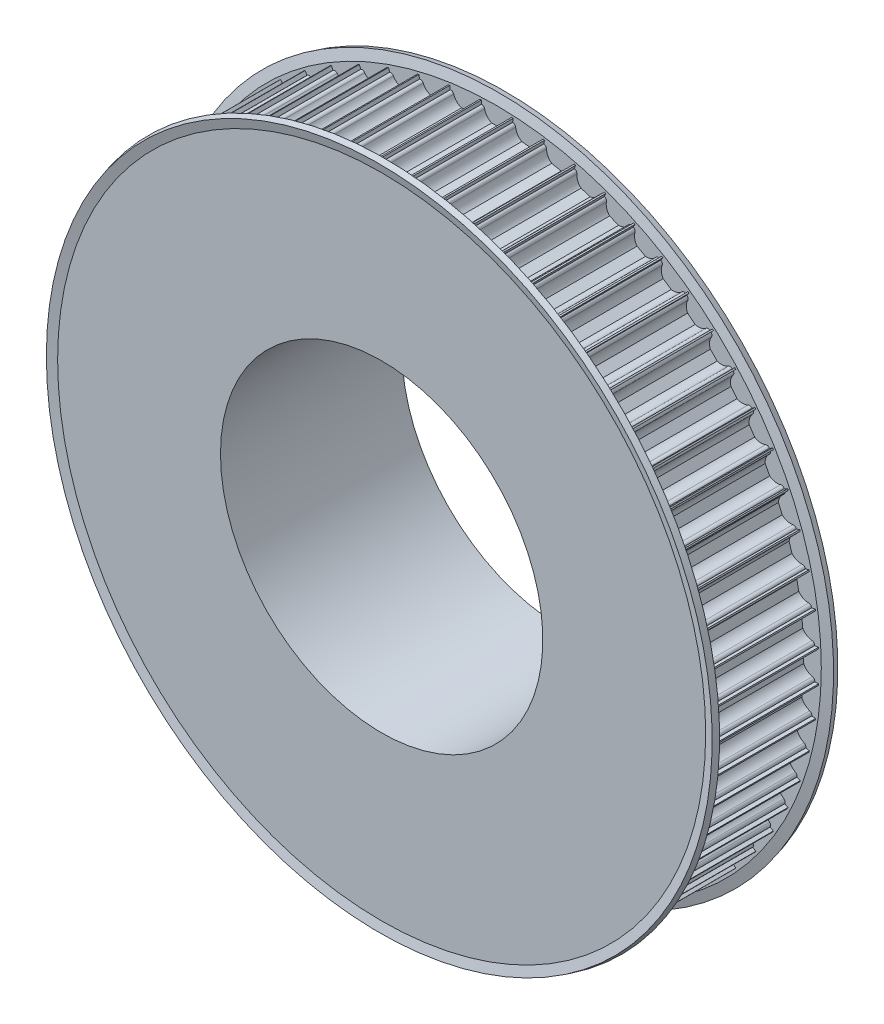
SolidWorks part; units mm, degrees
ref_plane "Front Plane" through (0, 0, 0) normal (0, 0, 1) x (1, 0, 0)
ref_plane "Top Plane" through (0, 0, 0) normal (0, 1, 0) x (1, 0, 0)
ref_plane "Right Plane" through (0, 0, 0) normal (1, 0, 0) x (0, 0, -1)
ref_axis "Axis1" through (0, 0, -88.99) along (0, 0, 1)
sketch "Sketch1" plane through (0, 0, 0) normal (1, 0, 0) x (0, 0, -1)
  line L0 (0, 40) -> (0, 80)
  line L1 (0, 80) -> (30, 80)
  line L2 (30, 80) -> (30, 55.5)
  line L3 (30, 55.5) -> (45, 55.5)
  line L4 (45, 55.5) -> (45, 40)
  line L5 (45, 40) -> (0, 40)
  dimension "D1" = 40
  dimension "D2" = 30
  dimension "D3" = 15
  dimension "D4" = 15.5
  dimension "D5" = 40
revolve "Revolve1" add sketch "Sketch1" angle 360 about axis through (0, 0, -88.99) along (0, 0, 1)
sketch "Sketch2" plane through (0, 0, 0) normal (0, 0, 1) x (1, 0, 0)
  line L0 (3.6742, 79) -> (3.75, 79)
  line L1 (-3.75, 81) -> (3.75, 81)
  line L2 (-3.75, 81) -> (-3.75, 79)
  line L3 (-3.75, 79) -> (-3.6742, 79)
  line L4 (3.75, 81) -> (3.75, 79)
  line L5 (-1.199, 76.25) -> (1.199, 76.25)
  arc A0 (-2.9394, 78.4) -> (-1.199, 76.25) centre (0, 79) ccw
  arc A1 (-2.9394, 78.4) -> (-3.6742, 79) centre (-3.6742, 78.25) ccw
  arc A2 (2.9394, 78.4) -> (3.6742, 79) centre (3.6742, 78.25) cw
  arc A3 (1.199, 76.25) -> (2.9394, 78.4) centre (0, 79) ccw
  dimension "D1" = 3
  dimension "D5" = 0.75
  dimension "D6" = 0.75
  dimension "D2" = 2
  dimension "D3" = 7.5
  dimension "D4" = 79
  dimension "D7" = 2.75
extrude "Cut-Extrude1" cut sketch "Sketch2" against normal through all
pattern_circular "CirPattern1" count 64 over 360 about axis through (0, 0, 0) along (0, 0, 1) of "Cut-Extrude1"
sketch "Sketch3" plane through (0, 0, 0) normal (1, 0, 0) x (0, 0, -1)
  line L8 (0, -37.0014) -> (0, -39.5498) construction
  line L25 (0, 75.6121) -> (1.5, 75.6121)
  line L26 (0, 75.6121) -> (0, 80.6121)
  line L27 (0, 80.6121) -> (1.5, 80.6121) construction
  line L28 (1.5, 75.6121) -> (1.5, 80.6121)
  line L29 (1.5, 80.6121) -> (0.0511, 80.2238) construction
  line L30 (1.5, 80.6121) -> (0.8569, 83.0121)
  line L31 (0.0511, 80.2238) -> (-0.592, 82.6238)
  line L32 (0.8569, 83.0121) -> (-0.592, 82.6238)
  line L33 (0, 79.9121) -> (30, 79.9121) construction
  line L34 (15, -40.9775) -> (15, -33.795) construction
  line L35 (30, -40.9775) -> (0, -40.9775) construction
  line L36 (28.5, 80.6121) -> (29.9489, 80.2238) construction
  line L37 (30, 80.6121) -> (28.5, 80.6121) construction
  line L38 (29.1431, 83.0121) -> (30.592, 82.6238)
  line L39 (29.9489, 80.2238) -> (30.592, 82.6238)
  line L40 (28.5, 80.6121) -> (29.1431, 83.0121)
  line L41 (28.5, 75.6121) -> (28.5, 80.6121)
  line L42 (30, 75.6121) -> (30, 80.6121)
  line L43 (30, 75.6121) -> (28.5, 75.6121)
  dimension "D1" = 1.5
  dimension "D2" = 5
  dimension "D3" = 1.5
  dimension "D4" = 165
  dimension "D5" = 2.4
  dimension "D6" = 0.7
revolve "Revolve2" add sketch "Sketch3" angle 360 about axis through (0, 0, -88.99) along (0, 0, 1)
